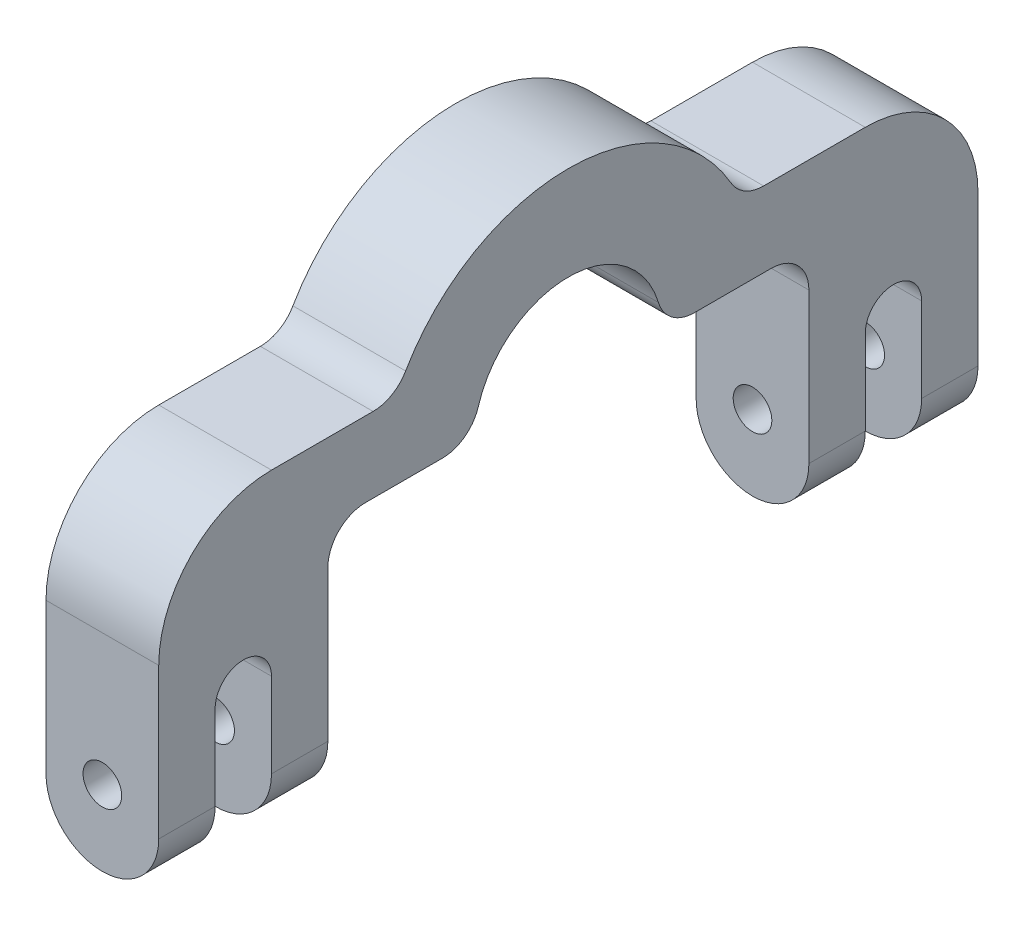
SolidWorks part; units mm, degrees
ref_plane "Front Plane" through (0, 0, 0) normal (0, 0, 1) x (1, 0, 0)
ref_plane "Top Plane" through (0, 0, 0) normal (0, 1, 0) x (1, 0, 0)
ref_plane "Right Plane" through (0, 0, 0) normal (1, 0, 0) x (0, 0, -1)
sketch "Sketch1" plane through (0, 0, 0) normal (0, 0, 1) x (1, 0, 0)
  line L0 (-4.7625, 0) -> (4.7625, 0)
  line L1 (-4.7625, 0) -> (-4.7625, -15.875)
  line L2 (4.7625, 0) -> (4.7625, -15.875)
  arc A0 (4.7625, -15.875) -> (-4.7625, -15.875) centre (0, -15.875) cw
  point P4 (0, 0)
  point P8 (0, 0)
  point P9 (-5.7154, -5.3688)
  point P10 (4.2254, -7.9297)
  point P11 (0, 0)
  point P12 (0, 0)
  point P13 (-3.3549, -9.8173)
  point P14 (0, 0)
  point P15 (0, 0)
  point P16 (0, -9.9058)
  point P17 (-4.8001, 0)
  point P18 (-3.1372, -10.683)
  point P19 (0, -10.3251)
  point P20 (4.808, 0)
  point P21 (0, -13.7379)
  dimension "D1" = 4.7625
  dimension "D2" = 9.525
  dimension "D3" = 15.875
extrude "Boss-Extrude1" add sketch "Sketch1" along normal mid plane 69.215
sketch "Sketch2" plane through (0, 0, 34.6075) normal (0, 0, 1) x (1, 0, 0)
  line L0 (-4.7625, -15.875) -> (-4.7625, -6.35)
  line L1 (-4.7625, 0) -> (-4.7625, -15.875) construction
  line L2 (-4.7625, -6.35) -> (4.7625, -6.35)
  line L3 (4.7625, -15.875) -> (4.7625, 0) construction
  line L4 (4.7625, -6.35) -> (4.7625, -15.875)
  line L5 (4.7625, 0) -> (-4.7625, 0) construction
  arc A0 (-4.7625, -15.875) -> (4.7625, -15.875) centre (0, -15.875) ccw construction
  arc A1 (-4.7625, -15.875) -> (4.7625, -15.875) centre (0, -15.875) ccw
  dimension "D1" = 6.35
extrude "Cut-Extrude1" cut sketch "Sketch2" against normal blind 4.7625 from offset 4.7625 offset against normal yes
sketch "Sketch3" plane through (0, 0, -34.6075) normal (0, 0, 1) x (1, 0, 0)
  line L0 (-4.7625, -15.875) -> (-4.7625, -6.35)
  line L2 (-4.7625, -6.35) -> (4.7625, -6.35)
  line L4 (4.7625, -6.35) -> (4.7625, -15.875)
  line L6 (-4.7625, 0) -> (-4.7625, -15.875) construction
  line L7 (4.7625, -15.875) -> (4.7625, 0) construction
  line L8 (4.7625, 0) -> (-4.7625, 0) construction
  arc A1 (-4.7625, -15.875) -> (4.7625, -15.875) centre (0, -15.875) ccw
  arc A2 (-4.7625, -15.875) -> (4.7625, -15.875) centre (0, -15.875) ccw construction
  point P3 (2.5097, -5.6469)
  point P9 (3.175, -12.7)
  point P10 (-4.9023, -5.964)
  point P13 (4.8812, -6.0508)
  dimension "D1" = 6.35
extrude "Cut-Extrude2" cut sketch "Sketch3" along normal blind 4.7625 from offset 4.7625
sketch "Sketch5" plane through (0, 0, 25.0825) normal (0, 0, 1) x (1, 0, 0)
  line L3 (4.7625, -15.875) -> (4.7625, 0)
  line L4 (4.7625, 0) -> (-4.7625, 0)
  line L5 (-4.7625, 0) -> (-4.7625, -15.875)
  line L6 (4.7625, -15.875) -> (4.7625, 0)
  line L7 (4.7625, 0) -> (-4.7625, 0)
  line L8 (-4.7625, 0) -> (-4.7625, -15.875)
  arc A1 (-4.7625, -15.875) -> (4.7625, -15.875) centre (0, -15.875) ccw
  arc A2 (-4.7625, -15.875) -> (4.7625, -15.875) centre (0, -15.875) ccw
  dimension "D1" = 0
extrude "Cut-Extrude3" cut sketch "Sketch5" against normal offset from surface (40.64 mm away) 4.7625 from offset 4.7625 up to face at (0, -12.3031, -25.0825) offset against normal yes
sketch "Sketch7" plane through (0, 0, 0) normal (0, 0, 1) x (1, 0, 0)
  line L0 (4.7625, 0) -> (4.7625, 6.35)
  line L1 (4.7625, 6.35) -> (-4.7625, 6.35)
  line L2 (-4.7625, 6.35) -> (-4.7625, 0)
  line L3 (4.7625, 0) -> (-4.7625, 0)
  dimension "D1" = 6.35
extrude "Boss-Extrude3" add sketch "Sketch7" against normal up to surface (34.6075 mm away) from surface up to face at (0, -9.1281, -34.6075) starting at face at (0, -9.1281, 34.6075)
fillet "Fillet1" radius 3.175 2 edges at (0, 0, 20.32) (0, 0, -20.32)
fillet "Fillet2" 2 edges at (0, -6.35, -29.845) (0, -6.35, -25.0825) type full round first side face at (0, -12.3031, -29.845) second side face at (0, -12.3031, -25.0825) middle face at (0, -6.35, -27.4638)
fillet "Fillet3" 2 edges at (0, -6.35, 25.0825) (0, -6.35, 29.845) type full round first side face at (0, -12.3031, 25.0825) second side face at (0, -12.3031, 29.845) middle face at (0, -6.35, 27.4638)
sketch "Sketch8" plane through (-4.7625, 0, 0) normal (-1, 0, 0) x (0, 0, 1)
  line L0 (-34.6075, 6.35) -> (34.6075, 6.35) construction
  line L1 (-14.5497, 6.35) -> (14.5497, 6.35)
  arc A0 (-14.5497, 6.35) -> (14.5497, 6.35) centre (0, 0) cw
  dimension "D1" = 15.875
extrude "Boss-Extrude4" add sketch "Sketch8" against normal up to surface (9.525 mm away) up to face at (4.7625, -8.3054, 0)
sketch "Sketch9" plane through (-4.7625, 0, 0) normal (-1, 0, 0) x (0, 0, 1)
  line L0 (-17.145, 0) -> (17.145, 0) construction
  line L1 (-7.9375, 0) -> (7.9375, 0)
  arc A0 (-7.9375, 0) -> (7.9375, 0) centre (0, 0) cw
  point P3 (0, 0)
  dimension "D1" = 15.875
extrude "Cut-Extrude4" cut sketch "Sketch9" against normal through all
fillet "Fillet4" radius 3.175 4 edges at (0, 6.35, 14.5497) (0, 6.35, -14.5497) (0, 0, 7.9375) (0, 0, -7.9375)
fillet "Fillet5" radius 9.525 2 edges at (0, 6.35, 34.6075) (0, 6.35, -34.6075)
hole_wizard "#4 Clearance Hole1" positions "Sketch10" profile "Sketch11" hole size "#4" standard "ANSI Inch" end condition through all
sketch "Sketch10" plane through (0, 0, -34.6075) normal (0, 0, -1) x (-1, 0, 0)
  arc A0 (-4.7625, -15.875) -> (4.7625, -15.875) centre (0, -15.875) ccw construction
  point P0 (0, -14.2875)
  point P6 (0, -20.6375)
  dimension "D1" = 6.35
sketch "Sketch11" plane through (0, -14.2875, -34.6075) normal (1, 0, 0) x (0, 1, 0)
  line L0 (0, 0) -> (0, 69.215)
  line L1 (0, 69.215) -> (1.6319, 69.215)
  line L2 (1.6319, 69.215) -> (1.6319, 0)
  line L5 (1.6319, 0) -> (0, 0)
  line L11 (0, -6.35) -> (0, 107.95) construction
  dimension "Thru Hole Dia." = 3.2639
  dimension "Thru Hole Depth" = 69.215
